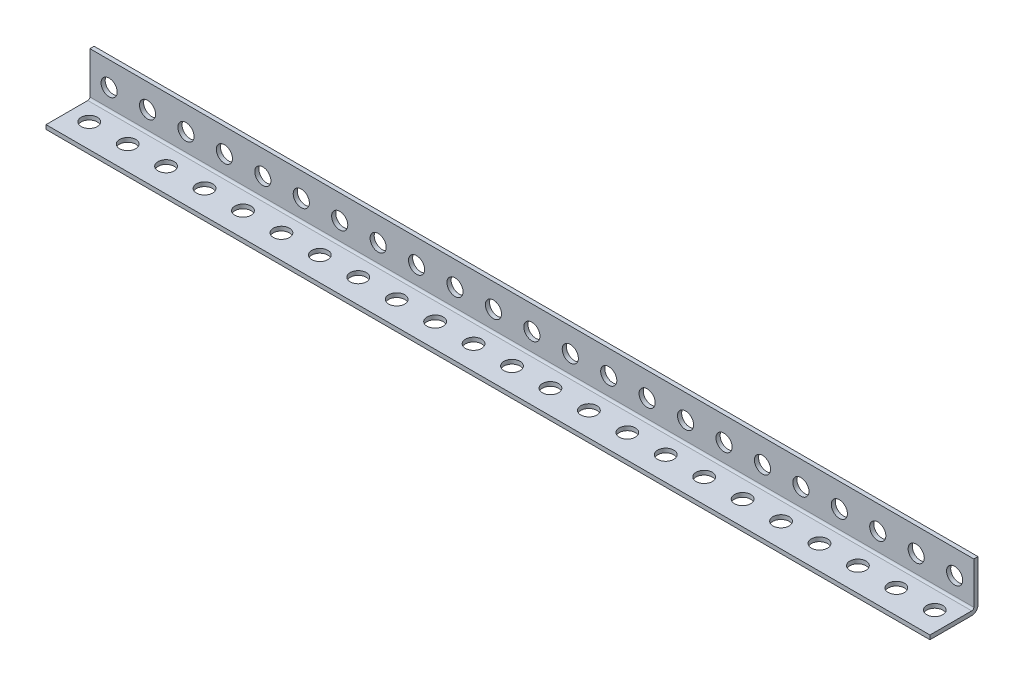
SolidWorks part; units mm, degrees
ref_plane "Front Plane" through (0, 0, 0) normal (0, 0, 1) x (1, 0, 0)
ref_plane "Top Plane" through (0, 0, 0) normal (0, 1, 0) x (1, 0, 0)
ref_plane "Right Plane" through (0, 0, 0) normal (1, 0, 0) x (0, 0, -1)
sketch "Sketch1" plane through (0, 0, 0) normal (1, 0, 0) x (0, 0, -1)
  line L0 (-15.875, -13.1318) -> (13.1318, -13.1318) construction
  line L1 (13.1318, -13.1318) -> (13.1318, 15.875) construction
  line L2 (13.1318, 15.875) -> (15.875, 15.875) construction
  line L3 (15.875, 15.875) -> (15.875, -15.875) construction
  line L4 (15.875, -15.875) -> (-15.875, -15.875) construction
  line L5 (-15.875, -15.875) -> (-15.875, -13.1318) construction
  line L6 (0, -15.875) -> (0, 15.875) construction
  line L7 (15.875, 0) -> (-15.875, 0) construction
  dimension "Thickness | T" = 2.7432
  dimension "Width (A)" = 31.75
  dimension "Width (B)" = 31.75
sketch "Sketch2" plane through (0, 0, 0) normal (0, 0, 1) x (1, 0, 0)
  line L0 (-609.6, 0) -> (609.6, 0) construction
  line L1 (-609.6, 15.875) -> (609.6, 15.875) construction
  line L2 (-609.6, 15.875) -> (-609.6, -15.875) construction
  line L3 (-609.6, -15.875) -> (609.6, -15.875) construction
  line L4 (609.6, 15.875) -> (609.6, -15.875) construction
  line L5 (0, 15.875) -> (0, -15.875) construction
  line L7 (-609.6, -13.1318) -> (609.6, -13.1318) construction
  circle A0 centre (596.9, 0) radius 5.334 construction
  circle A1 centre (571.5, 0) radius 5.334 construction
  point P15 (533.4, 0)
  point P16 (-533.4, 0)
  point P24 (602.234, 0)
  dimension "Mounting Hole Diameter" = 10.668
  dimension "Length | L" = 1219.2
  dimension "Mounting Hole Center to Center" = 25.4
  dimension "D1" = 12.7
  dimension "D2" = 63.5
sketch "Sketch3" plane through (0, 0, 0) normal (0, 1, 0) x (1, 0, 0)
  line L1 (-609.6, 15.875) -> (609.6, 15.875) construction
  line L2 (-609.6, 15.875) -> (-609.6, -15.875) construction
  line L3 (-609.6, -15.875) -> (609.6, -15.875) construction
  line L4 (609.6, 15.875) -> (609.6, -15.875) construction
  line L5 (-609.6, 13.1318) -> (609.6, 13.1318) construction
  line L7 (-609.6, 0) -> (609.6, 0) construction
  circle A0 centre (596.9, 0) radius 5.334 construction
  circle A1 centre (571.5, 0) radius 5.334 construction
  point P19 (-533.4, 0)
  point P21 (602.234, 0)
  point P22 (533.4, 0)
sketch "Sketch4" plane through (0, 0, 0) normal (1, 0, 0) x (0, 0, -1)
  line L0 (-15.875, -13.1318) -> (11.7602, -13.1318)
  line L1 (13.1318, -11.7602) -> (13.1318, 15.875)
  line L2 (13.1318, 15.875) -> (15.875, 15.875)
  line L3 (15.875, 15.875) -> (15.875, -11.7602)
  line L4 (11.7602, -15.875) -> (-15.875, -15.875)
  line L5 (-15.875, -15.875) -> (-15.875, -13.1318)
  line L6 (11.7602, -13.1318) -> (11.7602, -10.3886) construction
  arc A0 (11.7602, -13.1318) -> (13.1318, -11.7602) centre (11.7602, -11.7602) ccw
  arc A1 (15.875, -11.7602) -> (11.7602, -15.875) centre (11.7602, -11.7602) cw
extrude "Boss-Extrude1" add sketch "Sketch4" along normal up to vertex (609.6 mm away) and the other way up to vertex (609.6 mm away) up to point (609.6, 0, 0) other way up to point (-609.6, 0, 0)
sketch "Sketch5" plane through (0, 0, 0) normal (0, 0, 1) x (1, 0, 0)
  circle A0 centre (596.9, 0) radius 5.334
extrude "Cut-Extrude1" cut sketch "Sketch5" against normal through all
sketch "Sketch6" plane through (0, 0, 0) normal (0, 1, 0) x (1, 0, 0)
  circle A0 centre (596.9, 0) radius 5.334
extrude "Cut-Extrude2" cut sketch "Sketch6" against normal through all
pattern_linear "LPattern1" count 48 spacing 25.4 along (-1, 0, 0) of "Cut-Extrude2", "Cut-Extrude1"
sketch "Sketch7" plane through (0, 0, -15.875) normal (0, 0, -1) x (-1, 0, 0)
  line L0 (-609.6, -15.875) -> (609.6, -15.875) construction
  line L1 (-609.6, 15.875) -> (25.4, 15.875)
  line L2 (-609.6, 15.875) -> (-609.6, -15.875)
  line L3 (-609.6, -15.875) -> (25.4, -15.875)
  line L4 (25.4, 15.875) -> (25.4, -15.875)
  line L5 (602.234, 0) -> (609.6, 0) construction
  line L6 (609.6, -11.7602) -> (609.6, 15.875) construction
  line L7 (32.766, 0) -> (25.4, 0)
  circle A0 centre (596.9, 0) radius 5.334 construction
  circle A1 centre (38.1, 0) radius 5.334 construction
  dimension "D1" = 7.366
extrude "Cut-Extrude3" cut sketch "Sketch7" against normal blind 70 contours L4 L1 L2 L3 region at (292.1, 0, -15.875)
sketch "Sketch8" plane through (0, 0, -15.875) normal (0, 0, -1) x (-1, 0, 0)
  line L0 (602.234, 0) -> (609.6, 0)
  line L1 (609.6, -11.7602) -> (609.6, 15.875) construction
  line L2 (32.766, 0) -> (25.4, 0)
  line L3 (25.4, 15.875) -> (25.4, -11.7602) construction
  circle A0 centre (596.9, 0) radius 5.334 construction
  circle A1 centre (38.1, 0) radius 5.334 construction
sketch "Sketch9" plane through (0, -15.875, 0) normal (0, -1, 0) x (1, 0, 0)
  line L0 (-602.234, 0) -> (-609.6, 0)
  line L1 (-609.6, 15.875) -> (-609.6, -11.7602) construction
  line L2 (-32.766, 0) -> (-25.4, 0)
  line L3 (-25.4, 15.875) -> (-25.4, -11.7602) construction
  circle A0 centre (-596.9, 0) radius 5.334 construction
  circle A1 centre (-38.1, 0) radius 5.334 construction
equation "\"D1@Sketch2\"= ( \"Length | L@Sketch2\" - \"Mounting Hole Center to Center@Sketch2\" * \"Num Holes\" ) / 2"
equation "\"Num Holes\"= int ( \"Length | L@Sketch2\" / \"Mounting Hole Center to Center@Sketch2\" ) - 1"
equation "\"D2@Sketch2\"=\"Mounting Hole Center to Center@Sketch2\"*2.5"
equation "\"D3@LPattern1\"=\"Mounting Hole Center to Center@Sketch2\""
